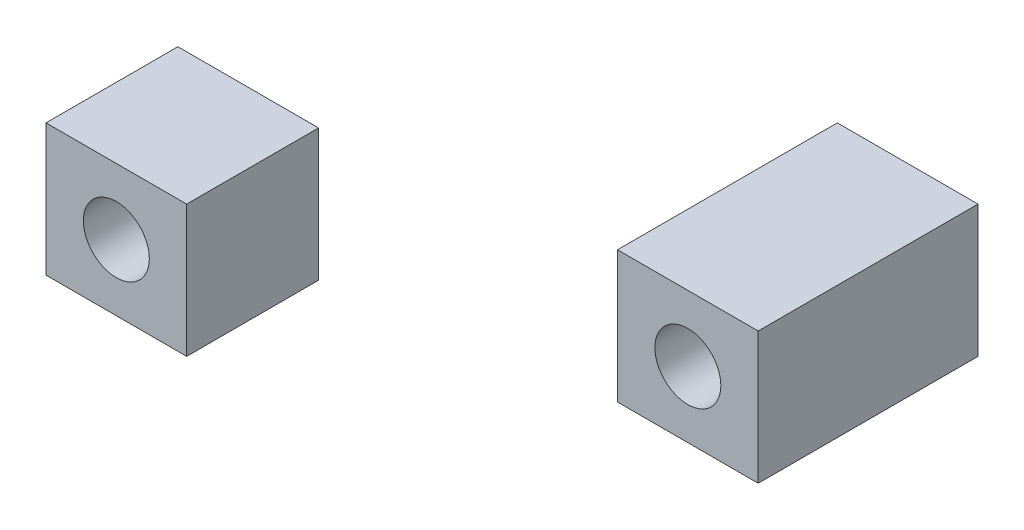
SolidWorks part; units mm, degrees
ref_plane "Front Plane" through (0, 0, 0) normal (0, 0, 1) x (1, 0, 0)
ref_plane "Top Plane" through (0, 0, 0) normal (0, 1, 0) x (1, 0, 0)
ref_plane "Right Plane" through (0, 0, 0) normal (1, 0, 0) x (0, 0, -1)
sketch "Sketch1" plane through (0, 0, 0) normal (0, 0, 1) x (1, 0, 0)
  line L1 (56, 50) -> (24, 50)
  line L2 (56, 50) -> (56, 20)
  line L3 (56, 20) -> (24, 20)
  line L4 (24, 50) -> (24, 20)
  line L5 (56, 50) -> (24, 20) construction
  line L6 (56, 20) -> (24, 50) construction
  line L7 (-34, 50) -> (-66, 50)
  line L8 (-34, 50) -> (-34, 20)
  line L9 (-34, 20) -> (-66, 20)
  line L10 (-66, 50) -> (-66, 20)
  line L11 (-34, 50) -> (-66, 20) construction
  line L12 (-34, 20) -> (-66, 50) construction
  circle A0 centre (40, 35) radius 7.5
  circle A1 centre (-50, 35) radius 7.5
  point P0 (40, 35)
  point P5 (-50, 35)
  point P14 (40, 35)
  dimension "D3" = 15
  dimension "D5" = 15
  dimension "D1" = 32
  dimension "D2" = 30
  dimension "D4" = 32
  dimension "D6" = 30
  dimension "D7" = 50
  dimension "D8" = 35
  dimension "D9" = 35
  dimension "D10" = 40
extrude "Boss-Extrude1" add sketch "Sketch1" along normal mid plane 50 contours L3 L4 L1 L2 | A0
extrude "Boss-Extrude2" add sketch "Sketch1<3>" along normal mid plane 30 from offset 50 separate body contours L8 L9 L10 L7 | A1
sketch "Sketch1<3>" plane through (0, 0, 0) normal (0, 0, 1) x (1, 0, 0) same geometry as "Sketch1"
